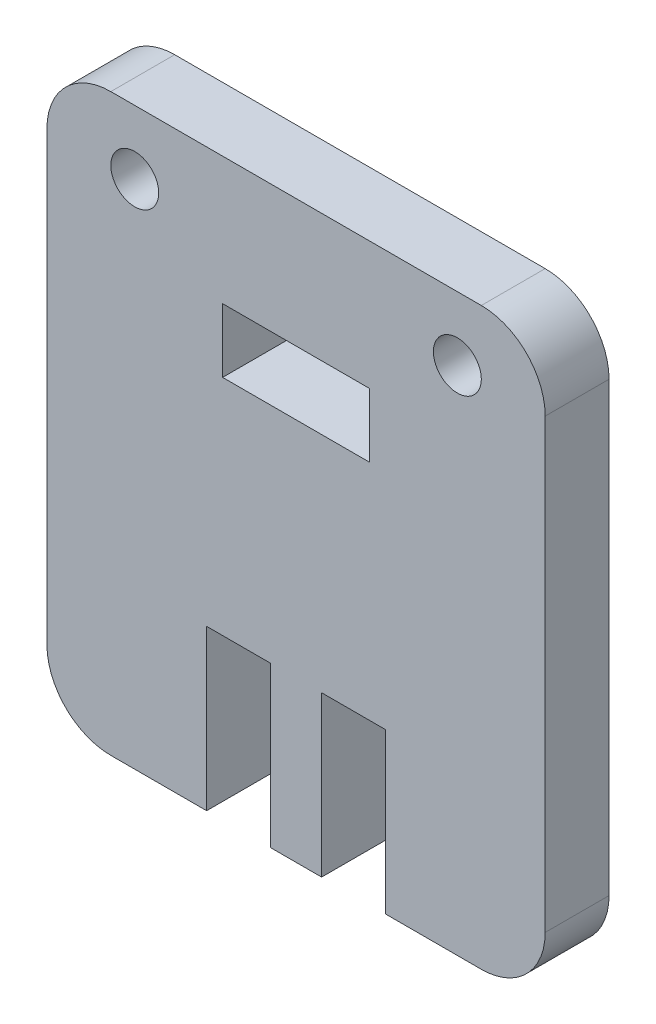
SolidWorks part; units mm, degrees
material "Acrylic (Medium-high impact)"
ref_plane "Front Plane" through (0, 0, 0) normal (0, 0, 1) x (1, 0, 0)
ref_plane "Top Plane" through (0, 0, 0) normal (0, 1, 0) x (1, 0, 0)
ref_plane "Right Plane" through (0, 0, 0) normal (1, 0, 0) x (0, 0, -1)
sketch "Model" plane through (0, 0, 0) normal (0, 0, 1) x (1, 0, 0)
  line L0 (2, 0) -> (5, 0)
  line L1 (5, 0) -> (5, 5)
  line L2 (5, 5) -> (7, 5)
  line L3 (7, 5) -> (7, 0)
  line L4 (7, 0) -> (8.6, 0)
  line L5 (8.6, 0) -> (8.6, 5)
  line L6 (8.6, 5) -> (10.6, 5)
  line L7 (10.6, 5) -> (10.6, 0)
  line L8 (10.6, 0) -> (13.6, 0)
  line L9 (0, 2) -> (0, 16)
  line L10 (2, 18) -> (13.6, 18)
  line L11 (15.6, 16) -> (15.6, 2)
  line L17 (5.5, 12) -> (10.1, 12)
  line L18 (10.1, 12) -> (10.1, 14)
  line L19 (10.1, 14) -> (5.5, 14)
  line L20 (5.5, 14) -> (5.5, 12)
  circle A0 centre (2.75, 16) radius 0.75
  circle A3 centre (12.85, 16) radius 0.75
  arc A4 (0, 16) -> (2, 18) centre (2, 16) cw
  arc A5 (2, 0) -> (0, 2) centre (2, 2) cw
  arc A6 (15.6, 2) -> (13.6, 0) centre (13.6, 2) cw
  arc A7 (13.6, 18) -> (15.6, 16) centre (13.6, 16) cw
  point P13 (0, 0)
  point P36 (0, 0)
  point P37 (0, 0)
  dimension "D1" = 1.5
  dimension "D2" = 2
  dimension "D3" = 15.6
  dimension "D4" = 13
  dimension "D10" = 5
  dimension "D13" = 2
other "AlignGroup1"
other "AlignGroup2"
other "AlignGroup3"
other "AlignGroup4"
other "AlignGroup5"
other "AlignGroup6"
other "AlignGroup7"
other "AlignGroup8"
extrude "Boss-Extrude1" add sketch "Model" along normal blind 2
